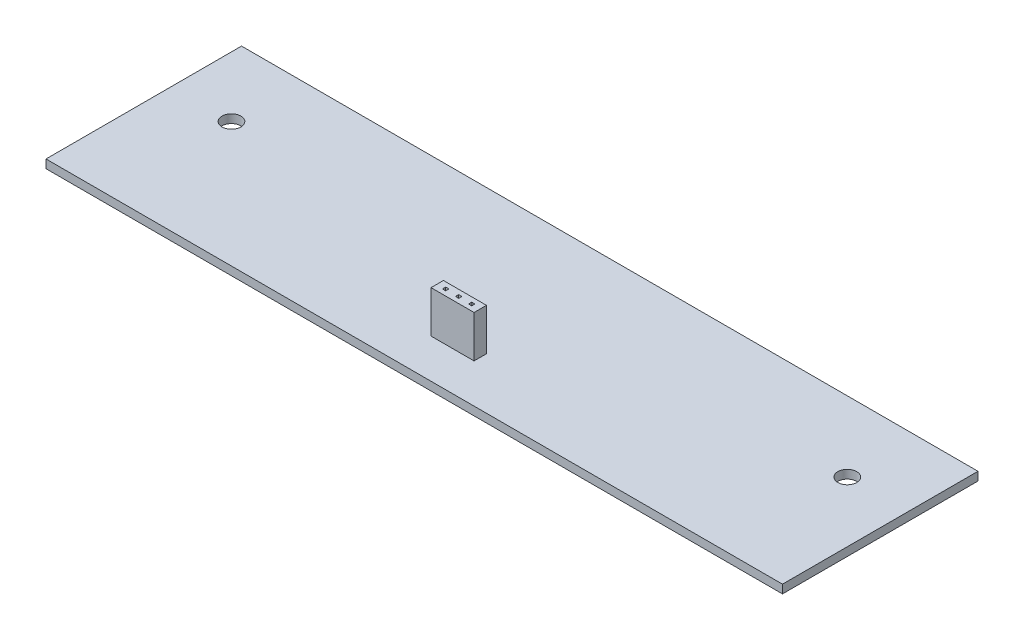
SolidWorks part; units mm, degrees
ref_plane "Plan de face" through (0, 0, 0) normal (0, 0, 1) x (1, 0, 0)
ref_plane "Plan de dessus" through (0, 0, 0) normal (0, 1, 0) x (1, 0, 0)
ref_plane "Plan de droite" through (0, 0, 0) normal (1, 0, 0) x (0, 0, -1)
sketch "Esquisse1" plane through (0, 0, 0) normal (0, 1, 0) x (1, 0, 0)
  line L1 (-71.755, 19.05) -> (71.755, 19.05)
  line L2 (-71.755, 19.05) -> (-71.755, -19.05)
  line L3 (-71.755, -19.05) -> (71.755, -19.05)
  line L4 (71.755, 19.05) -> (71.755, -19.05)
  line L5 (-71.755, 19.05) -> (71.755, -19.05) construction
  line L6 (-71.755, -19.05) -> (71.755, 19.05) construction
  point P0 (0, 0)
  dimension "D1" = 38.1
  dimension "D2" = 143.51
extrude "Boss.-Extru.1" add sketch "Esquisse1" along normal blind 1.651
sketch "Esquisse2" plane through (0, 1.651, 0) normal (0, 1, 0) x (1, 0, 0)
  line L0 (60, 19.05) -> (60, 5.334) construction
  line L1 (71.755, 19.05) -> (-71.755, 19.05) construction
  line L2 (71.755, 5.334) -> (60, 5.334) construction
  line L3 (71.755, -19.05) -> (71.755, 19.05) construction
  line L4 (0, 0) -> (0, 28.8871) construction
  line L5 (-60, 5.334) -> (60, 5.334) construction
  circle A0 centre (60, 5.334) radius 1.8415
  circle A1 centre (-60, 5.334) radius 1.8415
  dimension "D3" = 3.683
  dimension "D1" = 120
  dimension "D2" = 13.716
extrude "Enlèv. mat.-Extru.1" cut sketch "Esquisse2" against normal through all
sketch "Esquisse3" plane through (0, 1.651, 0) normal (0, 1, 0) x (1, 0, 0)
  line L0 (0, -19.05) -> (0, -11.43) construction
  line L1 (-71.755, -19.05) -> (71.755, -19.05) construction
  line L3 (-4.3457, -11.43) -> (-4.3457, -9.017)
  line L4 (-4.3457, -9.017) -> (4.0363, -9.017)
  line L5 (4.0363, -9.017) -> (4.0363, -11.43)
  line L7 (-4.3457, -11.43) -> (4.3457, -11.43)
  point P7 (0, -11.43)
  dimension "D1" = 7.62
  dimension "D2" = 8.382
  dimension "D3" = 2.413
extrude "Boss.-Extru.2" add sketch "Esquisse3" along normal blind 8.1788 contours L3 L7 L5 L4 region at (-0.1547, 1.651, 10.2235)
sketch "Esquisse4" plane through (0, 9.8298, 0) normal (0, 1, 0) x (1, 0, 0)
  line L0 (-0.1547, -9.017) -> (-0.1547, -11.43) construction
  line L1 (-4.3457, -9.017) -> (4.0363, -9.017) construction
  line L2 (-4.3457, -11.43) -> (4.0363, -11.43) construction
  line L3 (-4.3457, -9.017) -> (-0.1547, -9.017) construction
  line L4 (-0.4722, -9.906) -> (0.1628, -9.906)
  line L5 (-0.4722, -9.906) -> (-0.4722, -10.541)
  line L6 (-0.4722, -10.541) -> (0.1628, -10.541)
  line L7 (0.1628, -9.906) -> (0.1628, -10.541)
  line L8 (-0.4722, -9.906) -> (0.1628, -10.541) construction
  line L9 (-0.4722, -10.541) -> (0.1628, -9.906) construction
  line L10 (-0.1547, -9.017) -> (-2.6947, -9.017) construction
  line L11 (-2.6947, -9.017) -> (-2.6947, -11.43) construction
  line L12 (-0.1547, -9.017) -> (2.3853, -9.017) construction
  line L13 (-3.0122, -9.906) -> (-2.3772, -9.906)
  line L14 (-3.0122, -9.906) -> (-3.0122, -10.541)
  line L15 (-3.0122, -10.541) -> (-2.3772, -10.541)
  line L16 (-2.3772, -9.906) -> (-2.3772, -10.541)
  line L17 (-3.0122, -9.906) -> (-2.3772, -10.541) construction
  line L18 (-3.0122, -10.541) -> (-2.3772, -9.906) construction
  line L19 (2.3853, -9.017) -> (2.3853, -11.43) construction
  line L21 (2.0678, -9.906) -> (2.7028, -9.906)
  line L22 (2.0678, -9.906) -> (2.0678, -10.541)
  line L23 (2.0678, -10.541) -> (2.7028, -10.541)
  line L24 (2.7028, -9.906) -> (2.7028, -10.541)
  line L25 (2.0678, -9.906) -> (2.7028, -10.541) construction
  line L26 (2.0678, -10.541) -> (2.7028, -9.906) construction
  point P6 (-0.1547, -10.2235)
  point P12 (-2.6947, -10.2235)
  point P22 (2.3853, -10.2235)
  dimension "D1" = 0.635
  dimension "D2" = 0.635
  dimension "D3" = 2.54
  dimension "D4" = 0.635
  dimension "D5" = 0.635
  dimension "D6" = 2.54
  dimension "D7" = 0.635
  dimension "D8" = 0.635
extrude "Enlèv. mat.-Extru.2" cut sketch "Esquisse4" against normal blind 5.08
